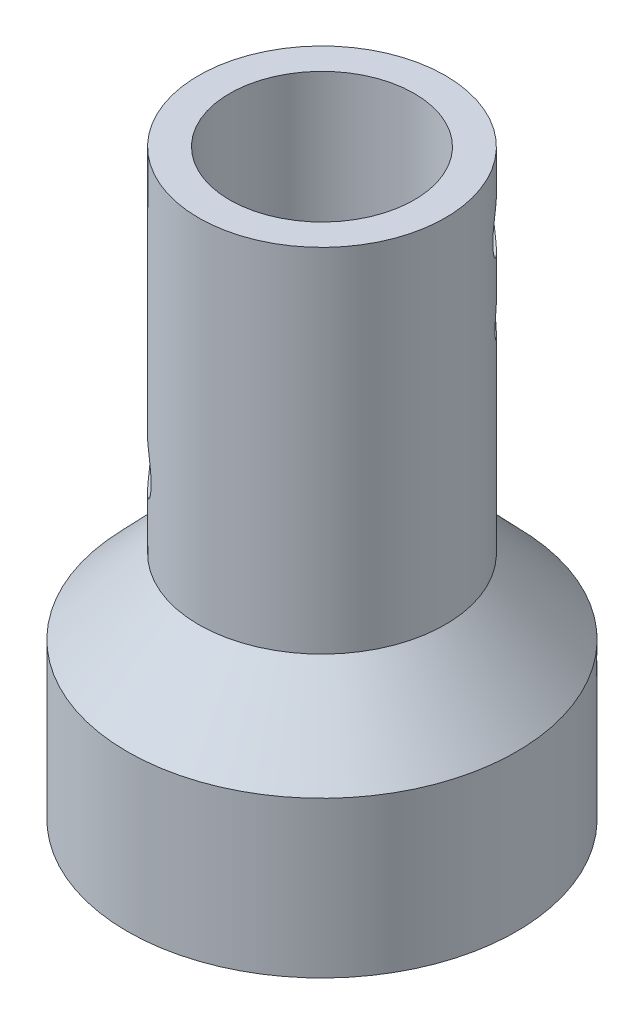
SolidWorks part; units mm, degrees
ref_plane "Front Plane" through (0, 0, 0) normal (0, 0, 1) x (1, 0, 0)
ref_plane "Top Plane" through (0, 0, 0) normal (0, 1, 0) x (1, 0, 0)
ref_plane "Right Plane" through (0, 0, 0) normal (1, 0, 0) x (0, 0, -1)
sketch "Sketch1" plane through (0, 0, 0) normal (0, 0, 1) x (1, 0, 0)
  line L0 (0, 0) -> (0, 70.35) construction
  line L1 (11.15, 20.4) -> (11.15, 70.35)
  line L2 (11.15, 70.35) -> (14.9, 70.35)
  line L3 (11.15, 20.4) -> (14.225, 20.4)
  line L4 (14.225, 20.4) -> (14.225, 0)
  line L5 (14.225, 0) -> (23.5, 0)
  line L6 (23.5, 0) -> (23.5, 18.8)
  line L7 (23.5, 18.8) -> (14.9, 27.8)
  line L8 (14.9, 27.8) -> (14.9, 70.35)
  dimension "D1" = 70.35
  dimension "D2" = 20.4
  dimension "D3" = 28.45
  dimension "D4" = 22.3
  dimension "D5" = 29.8
  dimension "D6" = 42.55
  dimension "D7" = 47
  dimension "D8" = 18.8
revolve "Revolve1" add sketch "Sketch1" angle 360 about L0
sketch "Sketch2" plane through (0, 0, 0) normal (0, -1, 0) x (1, 0, 0)
  line L0 (0, -21.275) -> (0, 21.275) construction
  line L1 (-3.3976, -3.3976) -> (3.3976, 3.3976) construction
  circle A0 centre (0, 19.625) radius 1.65
  circle A1 centre (0, -19.625) radius 1.65
  circle A2 centre (-19.625, 0) radius 1.65
  circle A3 centre (19.625, 0) radius 1.65
  point P2 (0, 0)
  point P10 (0, 0)
  dimension "D1" = 42.55
  dimension "D2" = 3.3
  dimension "D3" = 45
extrude "Cut-Extrude1" cut sketch "Sketch2" against normal blind 10
ref_plane "Plane1" through (0, 0, 0) normal (-0.7071, 0, 0.7071) x (0, -1, 0)
sketch "Sketch4" plane through (0, 0, 0) normal (-0.7071, 0, 0.7071) x (0, -1, 0)
  line L0 (-15.25, 0) -> (0, 0) construction
  line L1 (-65.35, 0) -> (-70.35, 0) construction
  line L2 (-70.35, 14.9) -> (-70.35, -14.9) construction
  line L3 (-54.35, 0) -> (-59.35, 0) construction
  line L4 (-40.15, 0) -> (-50.55, 0) construction
  circle A0 centre (-16.875, 0) radius 1.625
  circle A1 centre (-62.35, 0) radius 3
  circle A2 centre (-52.45, 0) radius 1.9
  circle A3 centre (-37.15, 0) radius 3
  dimension "D1" = 3.25
  dimension "D3" = 6
  dimension "D4" = 3.8
  dimension "D7" = 6
  dimension "D2" = 15.25
  dimension "D5" = 5
  dimension "D6" = 54.35
  dimension "D8" = 30.2
extrude "Cut-Extrude2" cut sketch "Sketch4" against normal through all contours A1 | A2 | A0
extrude "Cut-Extrude3" cut sketch "Sketch4<3>" along normal through all contours A3 region at (0, 37.15, 0)
sketch "Sketch4<3>" plane through (0, 0, 0) normal (-0.7071, 0, 0.7071) x (0, -1, 0) same geometry as "Sketch4"
